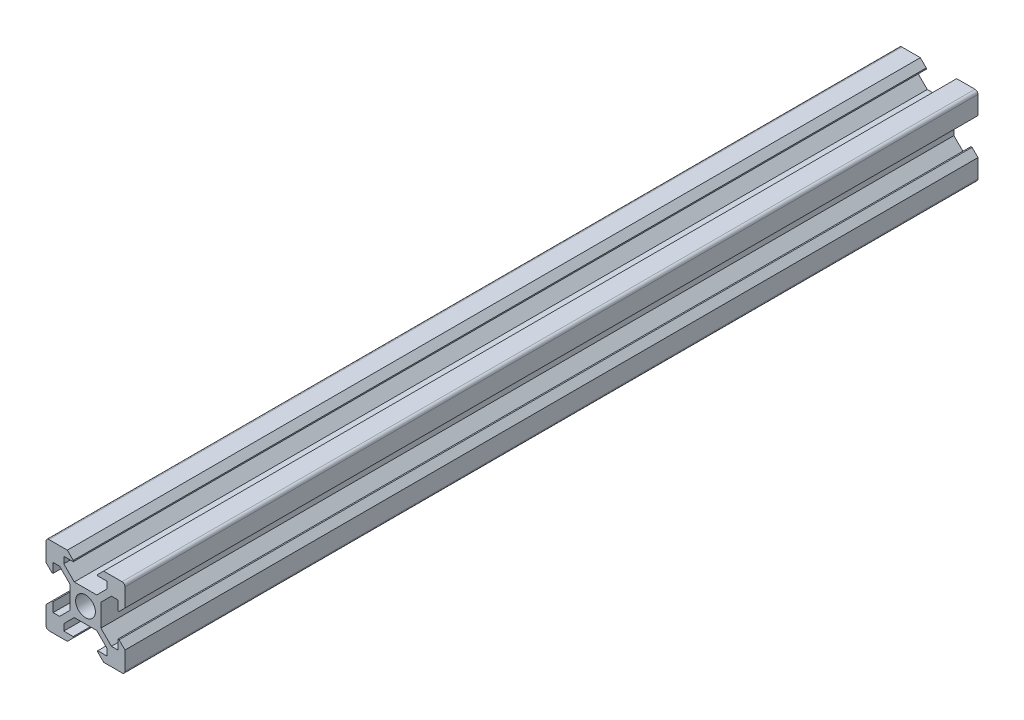
SolidWorks part; units mm, degrees
other "Markup1"
sketch "Sketch1" plane through (10, 10, 480) normal (0.5774, 0.5773, 0.5774) x (0.7071, 0, -0.7071)
ref_plane "Alzado" through (0, 0, 0) normal (0, 0, 1) x (1, 0, 0)
ref_plane "Planta" through (0, 0, 0) normal (0, 1, 0) x (1, 0, 0)
ref_plane "Vista lateral" through (0, 0, 0) normal (1, 0, 0) x (0, 0, -1)
sketch "Croquis1" plane through (0, 0, 0) normal (0, 0, 1) x (1, 0, 0)
  line L0 (-4.6, 10) -> (-3.1, 8.5)
  line L3 (-4.6, 10) -> (-9.25, 10)
  line L5 (-3.1, 8.5) -> (-3.1, 8.2)
  line L6 (-3.1, 8.2) -> (-5.5, 8.2)
  line L7 (-5.5, 8.2) -> (-5.5, 6.5607)
  line L8 (-5.5, 6.5607) -> (-2.84, 3.9007)
  line L9 (-2.84, 3.9007) -> (0, 3.9007)
  line L10 (0, 0) -> (-15.3499, 15.3499) construction
  line L11 (-3.9007, 2.84) -> (-3.9007, 0)
  line L12 (-6.5607, 5.5) -> (-3.9007, 2.84)
  line L13 (-8.2, 5.5) -> (-6.5607, 5.5)
  line L14 (-8.2, 3.1) -> (-8.2, 5.5)
  line L15 (-8.5, 3.1) -> (-8.2, 3.1)
  line L16 (-10, 4.6) -> (-10, 9.25)
  line L17 (-10, 4.6) -> (-8.5, 3.1)
  line L18 (10, 4.6) -> (8.5, 3.1)
  line L19 (10, 4.6) -> (10, 9.25)
  line L20 (8.5, 3.1) -> (8.2, 3.1)
  line L21 (8.2, 3.1) -> (8.2, 5.5)
  line L22 (8.2, 5.5) -> (6.5607, 5.5)
  line L23 (6.5607, 5.5) -> (3.9007, 2.84)
  line L24 (3.9007, 2.84) -> (3.9007, 0)
  line L25 (5.5, 6.5607) -> (2.84, 3.9007)
  line L26 (5.5, 8.2) -> (5.5, 6.5607)
  line L27 (3.1, 8.2) -> (5.5, 8.2)
  line L28 (3.1, 8.5) -> (3.1, 8.2)
  line L29 (4.6, 10) -> (9.25, 10)
  line L30 (4.6, 10) -> (3.1, 8.5)
  line L31 (2.84, 3.9007) -> (0, 3.9007)
  line L32 (4.6, -10) -> (3.1, -8.5)
  line L33 (4.6, -10) -> (9.25, -10)
  line L34 (3.1, -8.5) -> (3.1, -8.2)
  line L35 (3.1, -8.2) -> (5.5, -8.2)
  line L36 (5.5, -8.2) -> (5.5, -6.5607)
  line L37 (5.5, -6.5607) -> (2.84, -3.9007)
  line L38 (2.84, -3.9007) -> (0, -3.9007)
  line L39 (6.5607, -5.5) -> (3.9007, -2.84)
  line L40 (8.2, -5.5) -> (6.5607, -5.5)
  line L41 (8.2, -3.1) -> (8.2, -5.5)
  line L42 (8.5, -3.1) -> (8.2, -3.1)
  line L43 (10, -4.6) -> (10, -9.25)
  line L44 (10, -4.6) -> (8.5, -3.1)
  line L45 (3.9007, -2.84) -> (3.9007, 0)
  line L46 (-10, -4.6) -> (-8.5, -3.1)
  line L47 (-10, -4.6) -> (-10, -9.25)
  line L48 (-8.5, -3.1) -> (-8.2, -3.1)
  line L49 (-8.2, -3.1) -> (-8.2, -5.5)
  line L50 (-8.2, -5.5) -> (-6.5607, -5.5)
  line L51 (-6.5607, -5.5) -> (-3.9007, -2.84)
  line L52 (-3.9007, -2.84) -> (-3.9007, 0)
  line L53 (-5.5, -6.5607) -> (-2.84, -3.9007)
  line L54 (-5.5, -8.2) -> (-5.5, -6.5607)
  line L55 (-3.1, -8.2) -> (-5.5, -8.2)
  line L56 (-3.1, -8.5) -> (-3.1, -8.2)
  line L57 (-4.6, -10) -> (-9.25, -10)
  line L58 (-4.6, -10) -> (-3.1, -8.5)
  line L59 (-2.84, -3.9007) -> (0, -3.9007)
  circle A0 centre (0, 0) radius 2.5
  arc A1 (-9.25, 10) -> (-10, 9.25) centre (-9.25, 9.25) ccw
  arc A2 (10, 9.25) -> (9.25, 10) centre (9.25, 9.25) ccw
  arc A3 (9.25, -10) -> (10, -9.25) centre (9.25, -9.25) ccw
  arc A4 (-10, -9.25) -> (-9.25, -10) centre (-9.25, -9.25) ccw
  point P18 (-10, 10)
  point P37 (10, 10)
  point P55 (10, -10)
  point P73 (-10, -10)
  point P79 (0, 0)
  dimension "D1" = 5
  dimension "D5" = 0.75
  dimension "D2" = 10
  dimension "D3" = 10
  dimension "D4" = 4.6
  dimension "D6" = 5.5
  dimension "D7" = 135
  dimension "D8" = 0.75
  dimension "D9" = 225
  dimension "D10" = 2.84
  dimension "D11" = 1.8
  dimension "D12" = 3.1
  dimension "D13" = 4
extrude "Saliente-Extruir1" add sketch "Croquis1" along normal blind 215.95
